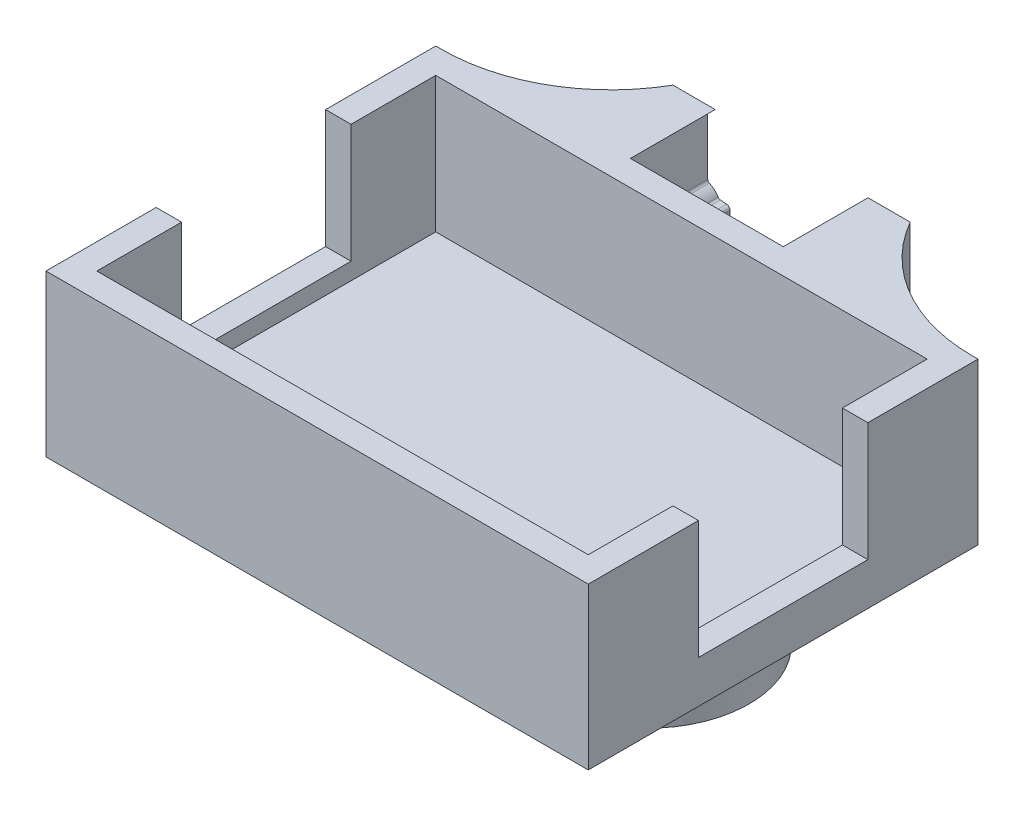
SolidWorks part; units mm, degrees
ref_plane "Front Plane" through (0, 0, 0) normal (0, 0, 1) x (1, 0, 0)
ref_plane "Top Plane" through (0, 0, 0) normal (0, 1, 0) x (1, 0, 0)
ref_plane "Right Plane" through (0, 0, 0) normal (1, 0, 0) x (0, 0, -1)
sketch "Sketch4" plane through (0, 0, 0) normal (0, 1, 0) x (1, 0, 0)
  line L1 (-16, -11.5) -> (16, -11.5)
  line L2 (-16, -11.5) -> (-16, 11.5)
  line L3 (-16, 11.5) -> (16, 11.5)
  line L4 (16, -11.5) -> (16, 11.5)
  line L5 (-16, -11.5) -> (16, 11.5) construction
  line L6 (-16, 11.5) -> (16, -11.5) construction
  point P0 (0, 0)
  dimension "D1" = 32
  dimension "D2" = 23
extrude "Boss-Extrude3" add sketch "Sketch4" along normal blind 9.5
sketch "Sketch5" plane through (0, 9.5, 0) normal (0, 1, 0) x (1, 0, 0)
  line L1 (-14.5, -10) -> (14.5, -10)
  line L2 (-14.5, -10) -> (-14.5, 10)
  line L3 (-14.5, 10) -> (14.5, 10)
  line L4 (14.5, -10) -> (14.5, 10)
  line L5 (-14.5, -10) -> (14.5, 10) construction
  line L6 (-14.5, 10) -> (14.5, -10) construction
  point P0 (0, 0)
  dimension "D1" = 29
  dimension "D2" = 20
extrude "Cut-Extrude2" cut sketch "Sketch5" against normal blind 8
sketch "Sketch8" plane through (-16, 0, 0) normal (-1, 0, 0) x (0, 0, 1)
  line L2 (-11.5, 9.5) -> (11.5, 9.5) construction
  line L4 (11.5, 9.5) -> (11.5, 0) construction
  line L8 (-2.2, 9.5) -> (-1.4, 9.5)
  spline S0 degree 3 poles (-2.2, 9.5) (-2.1353, 9.2413) (-1.5778, 9.0675) (-1.4, 9.5) knots 0 0 0 0 1 1 1 1
  line B0 (4.5, 6.0583) -> (4.5, 9.1)
  line B1 (4.5, 9.1) -> (4.1, 9.5)
  line B2 (4.1, 9.5) -> (-1.4, 9.5)
  line B3 (-2.2, 9.5) -> (-4.1, 9.5)
  line B4 (-4.1, 9.5) -> (-4.5, 9.1)
  line B5 (-4.5, 9.1) -> (-4.5, 6.0583)
  line B6 (-3.8235, 5.4365) -> (-3.4826, 5.4066)
  line B7 (-3.3, 5.2074) -> (-3.3, 4.7926)
  line B8 (-3.4826, 4.5934) -> (-3.8235, 4.5635)
  line B9 (-4.5, 3.9417) -> (-4.5, 3.4)
  line B10 (-4.5, 3.4) -> (-4.1, 3)
  line B11 (-4.1, 3) -> (4.1, 3)
  line B12 (4.1, 3) -> (4.5, 3.4)
  line B13 (4.5, 3.4) -> (4.5, 3.9417)
  line B14 (3.8235, 4.5635) -> (3.4826, 4.5934)
  line B15 (3.3, 4.7926) -> (3.3, 5.2074)
  line B16 (3.4826, 5.4066) -> (3.8235, 5.4365)
  arc B17 (-2.2, 9.5) -> (-1.4, 9.5) centre (-1.8, 9.8) ccw
  arc B18 (-4.5, 6.0583) -> (-4.4087, 5.9203) centre (-4.35, 6.0583) ccw
  arc B19 (-3.9395, 5.5095) -> (-4.4087, 5.9203) centre (-4.8, 5) ccw
  arc B20 (-3.9395, 5.5095) -> (-3.8235, 5.4365) centre (-3.8104, 5.5859) ccw
  arc B21 (-3.3, 5.2074) -> (-3.4826, 5.4066) centre (-3.5, 5.2074) ccw
  arc B22 (-3.4826, 4.5934) -> (-3.3, 4.7926) centre (-3.5, 4.7926) ccw
  arc B23 (-3.8235, 4.5635) -> (-3.9395, 4.4905) centre (-3.8104, 4.4141) ccw
  arc B24 (-4.4087, 4.0797) -> (-3.9395, 4.4905) centre (-4.8, 5) ccw
  arc B25 (-4.4087, 4.0797) -> (-4.5, 3.9417) centre (-4.35, 3.9417) ccw
  arc B26 (4.5, 3.9417) -> (4.4087, 4.0797) centre (4.35, 3.9417) ccw
  arc B27 (3.9395, 4.4905) -> (4.4087, 4.0797) centre (4.8, 5) ccw
  arc B28 (3.9395, 4.4905) -> (3.8235, 4.5635) centre (3.8104, 4.4141) ccw
  arc B29 (3.3, 4.7926) -> (3.4826, 4.5934) centre (3.5, 4.7926) ccw
  arc B30 (3.4826, 5.4066) -> (3.3, 5.2074) centre (3.5, 5.2074) ccw
  arc B31 (3.8235, 5.4365) -> (3.9395, 5.5095) centre (3.8104, 5.5859) ccw
  arc B32 (4.4087, 5.9203) -> (3.9395, 5.5095) centre (4.8, 5) ccw
  arc B33 (4.4087, 5.9203) -> (4.5, 6.0583) centre (4.35, 6.0583) ccw
  line M194 (11.5, 9.5) -> (-11.5, 9.5)
  dimension "D1" = 7
sketch_block_instance "9mm Block-2"
sketch_block "9mm Block"
extrude "Cut-Extrude4" cut sketch "Sketch8" against normal up to surface (32 mm away) contours B32 B33 B0 B1 S0 B4 B5 B18 B19 B20 B6 B21 B7 B22 B8 B23 B24 B25 B9 B10 B11 B12 B13 B26 B27 B28 B14 B29 B15 B30 B16 B31 M194 | B17 M194 | B17 S0 region at (-16, 9.2916, -1.8) region at (-16, 6.3052, 0.005) region at (-16, 9.4184, -1.8) up to face at (16, 4.75, 0)
sketch "Sketch9" plane through (0, 0, 0) normal (0, -1, 0) x (-1, 0, 0)
  line L0 (16, -11.5) -> (-16, -11.5) construction
  line L1 (0, -11.5) -> (0, 11.5) construction
  line L2 (-16, 11.5) -> (16, 11.5) construction
  line L3 (0, -11.5) -> (16, 11.5) construction
  line L4 (16, -11.5) -> (0, 11.5) construction
  circle A0 centre (8, 0) radius 4.8125
  circle A1 centre (8, 0) radius 6
  circle A2 centre (-8, 0) radius 4.8125
  circle A3 centre (-8, 0) radius 6
  dimension "D1" = 9.625
  dimension "D2" = 12
extrude "Boss-Extrude5" add sketch "Sketch9" along normal blind 3.375 contours A1 | A3 | A2 | A0
sketch "Sketch12" plane through (-16, 0, 0) normal (-1, 0, 0) x (0, 0, 1)
  line L0 (4.1, 9.5) -> (11.5, 9.5) construction
  line L5 (-5, 2.5) -> (5, 2.5)
  line L6 (-5, 2.5) -> (-5, 9.5)
  line L7 (-5, 9.5) -> (5, 9.5)
  line L8 (5, 2.5) -> (5, 9.5)
  line L9 (-5, 2.5) -> (5, 9.5) construction
  line L10 (-5, 9.5) -> (5, 2.5) construction
  line L11 (11.5, 9.5) -> (11.5, 0) construction
  point P4 (0, 6)
  dimension "D1" = 10
  dimension "D2" = 7
  dimension "D3" = 6.5
extrude "Cut-Extrude5" cut sketch "Sketch12" against normal up to surface (32 mm away) up to face at (16, 5.25, 0)
sketch "Sketch15" plane through (0, 0, -11.5) normal (0, 0, -1) x (-1, 0, 0)
  line L0 (-16, 9.5) -> (16, 9.5) construction
  line L1 (-16, 0) -> (16, 0) construction
  line L2 (16, 9.5) -> (16, 0) construction
  line L3 (-7, 9.5) -> (7, 9.5)
  line L4 (-7, 9.5) -> (-7, 0)
  line L5 (-7, 0) -> (7, 0)
  line L6 (7, 9.5) -> (7, 0)
  line L7 (-7, 9.5) -> (7, 0) construction
  line L8 (-7, 0) -> (7, 9.5) construction
  point P8 (0, 2.35)
  point P14 (0, 4.75)
  line B0 (4.95, 5.7141) -> (4.95, 9.06)
  line B1 (4.95, 9.06) -> (4.51, 9.5)
  line B2 (4.51, 9.5) -> (-1.54, 9.5)
  line B3 (-2.42, 9.5) -> (-4.51, 9.5)
  line B4 (-4.51, 9.5) -> (-4.95, 9.06)
  line B5 (-4.95, 9.06) -> (-4.95, 5.7141)
  line B6 (-4.2059, 5.0301) -> (-3.8308, 4.9973)
  line B7 (-3.63, 4.7781) -> (-3.63, 4.3219)
  line B8 (-3.8308, 4.1027) -> (-4.2059, 4.0699)
  line B9 (-4.95, 3.3859) -> (-4.95, 2.79)
  line B10 (-4.95, 2.79) -> (-4.51, 2.35)
  line B11 (-4.51, 2.35) -> (4.51, 2.35)
  line B12 (4.51, 2.35) -> (4.95, 2.79)
  line B13 (4.95, 2.79) -> (4.95, 3.3859)
  line B14 (4.2059, 4.0699) -> (3.8308, 4.1027)
  line B15 (3.63, 4.3219) -> (3.63, 4.7781)
  line B16 (3.8308, 4.9973) -> (4.2059, 5.0301)
  arc B17 (-2.42, 9.5) -> (-1.54, 9.5) centre (-1.98, 9.83) ccw
  arc B18 (-4.95, 5.7141) -> (-4.8496, 5.5623) centre (-4.785, 5.7141) ccw
  arc B19 (-4.3335, 5.1104) -> (-4.8496, 5.5623) centre (-5.28, 4.55) ccw
  arc B20 (-4.3335, 5.1104) -> (-4.2059, 5.0301) centre (-4.1915, 5.1945) ccw
  arc B21 (-3.63, 4.7781) -> (-3.8308, 4.9973) centre (-3.85, 4.7781) ccw
  arc B22 (-3.8308, 4.1027) -> (-3.63, 4.3219) centre (-3.85, 4.3219) ccw
  arc B23 (-4.2059, 4.0699) -> (-4.3335, 3.9896) centre (-4.1915, 3.9055) ccw
  arc B24 (-4.8496, 3.5377) -> (-4.3335, 3.9896) centre (-5.28, 4.55) ccw
  arc B25 (-4.8496, 3.5377) -> (-4.95, 3.3859) centre (-4.785, 3.3859) ccw
  arc B26 (4.95, 3.3859) -> (4.8496, 3.5377) centre (4.785, 3.3859) ccw
  arc B27 (4.3335, 3.9896) -> (4.8496, 3.5377) centre (5.28, 4.55) ccw
  arc B28 (4.3335, 3.9896) -> (4.2059, 4.0699) centre (4.1915, 3.9055) ccw
  arc B29 (3.63, 4.3219) -> (3.8308, 4.1027) centre (3.85, 4.3219) ccw
  arc B30 (3.8308, 4.9973) -> (3.63, 4.7781) centre (3.85, 4.7781) ccw
  arc B31 (4.2059, 5.0301) -> (4.3335, 5.1104) centre (4.1915, 5.1945) ccw
  arc B32 (4.8496, 5.5623) -> (4.3335, 5.1104) centre (5.28, 4.55) ccw
  arc B33 (4.8496, 5.5623) -> (4.95, 5.7141) centre (4.785, 5.7141) ccw
  line M2 (-16, 0) -> (16, 0)
  line M4 (16, 9.5) -> (-16, 9.5)
  dimension "D1" = 14
  dimension "D2" = 9
sketch_block_instance "9mm Block-7"
extrude "Boss-Extrude7" add sketch "Sketch15" along normal blind 5 contours B33 B32 B31 B16 B30 B15 B29 B14 B28 B27 B26 B13 B12 B11 B10 B9 B25 B24 B23 B8 B22 B7 B21 B6 B20 B19 B18 B5 B4 L4 L6 B1 B0 M4 M2 region at (5.755, 9.3308, -11.5)
fillet "Fillet1" radius 10 2 edges at (-7, 4.75, -11.5) (7, 4.75, -11.5)
